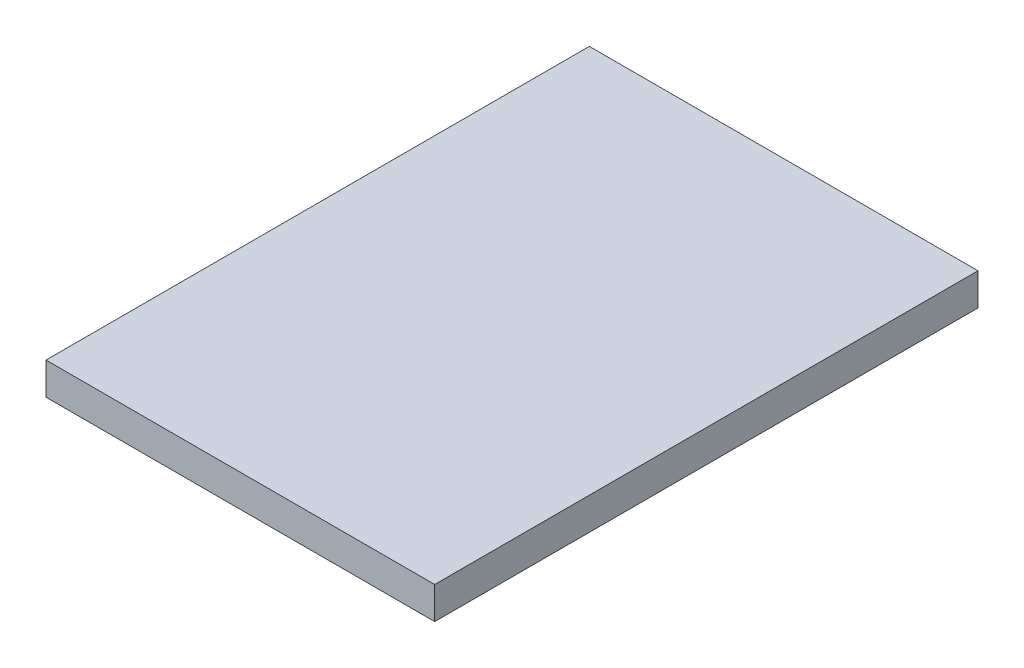
SolidWorks part; units mm, degrees
ref_plane "Front Plane" through (0, 0, 0) normal (0, 0, 1) x (1, 0, 0)
ref_plane "Top Plane" through (0, 0, 0) normal (0, 1, 0) x (1, 0, 0)
ref_plane "Right Plane" through (0, 0, 0) normal (1, 0, 0) x (0, 0, -1)
sketch "Sketch1" plane through (0, 0, 0) normal (0, 1, 0) x (1, 0, 0)
  line L1 (-9.3, -13) -> (9.3, -13)
  line L2 (-9.3, -13) -> (-9.3, 13)
  line L3 (-9.3, 13) -> (9.3, 13)
  line L4 (9.3, -13) -> (9.3, 13)
  line L5 (-9.3, -13) -> (9.3, 13) construction
  line L6 (-9.3, 13) -> (9.3, -13) construction
  point P0 (0, 0)
  dimension "D1" = 18.6
  dimension "D2" = 26
extrude "Boss-Extrude1" add sketch "Sketch1" along normal blind 1.54
sketch "Sketch2" plane through (0, 1.54, 0) normal (0, 1, 0) x (1, 0, 0)
  line L0 (-9.3, -13) -> (9.3, -13) construction
  line L1 (-5.25, -6) -> (5.25, -6)
  line L2 (-5.25, -6) -> (-5.25, -11)
  line L3 (-5.25, -11) -> (5.25, -11)
  line L4 (5.25, -6) -> (5.25, -11)
  line L5 (-5.25, -6) -> (5.25, -11) construction
  line L6 (-5.25, -11) -> (5.25, -6) construction
  line L7 (0, -8.5) -> (0, 0) construction
  point P0 (0, -8.5)
  dimension "D1" = 10.5
  dimension "D2" = 5
  dimension "D3" = 2
extrude "Boss-Extrude2" [suppressed] add sketch "Sketch2" along normal blind 8.5 separate body
sketch "Sketch3" plane through (0, 0, 0) normal (0, -1, 0) x (1, 0, 0)
  line L0 (-9.3, 13) -> (9.3, 13) construction
  line L1 (-6.75, 0.69) -> (6.75, 0.69)
  line L2 (-6.75, 0.69) -> (-6.75, 3.23)
  line L3 (-6.75, 3.23) -> (6.75, 3.23)
  line L4 (6.75, 0.69) -> (6.75, 3.23)
  line L5 (-6.75, 0.69) -> (6.75, 3.23) construction
  line L6 (-6.75, 3.23) -> (6.75, 0.69) construction
  line L7 (0, 1.96) -> (0, 0) construction
  point P0 (0, 1.96)
  dimension "D1" = 2.54
  dimension "D2" = 13.5
  dimension "D3" = 12.31
extrude "Boss-Extrude3" [suppressed] add sketch "Sketch3" along normal blind 2 and the other way offset from surface 7.8 separate body other way up to face at (0, 1.54, 0)
sketch "Sketch4" plane through (0, 0, 0) normal (0, -1, 0) x (1, 0, 0)
  line L0 (-9.3, -13) -> (-9.3, 13) construction
  line L1 (-6.3, -6.45) -> (-8.84, -6.45)
  line L2 (-6.3, -6.45) -> (-6.3, -11.63)
  line L3 (-6.3, -11.63) -> (-8.84, -11.63)
  line L4 (-8.84, -6.45) -> (-8.84, -11.63)
  line L5 (-6.3, -6.45) -> (-8.84, -11.63) construction
  line L6 (-6.3, -11.63) -> (-8.84, -6.45) construction
  line L7 (9.3, -13) -> (-9.3, -13) construction
  point P0 (-7.57, -9.04)
  dimension "D1" = 2.54
  dimension "D2" = 5.18
  dimension "D3" = 3
  dimension "D4" = 6.55
extrude "Boss-Extrude4" [suppressed] add sketch "Sketch4" along normal up to surface and the other way up to surface separate body up to face at (0, 1.54, 0) other way up to face at (0, 1.54, 0)
